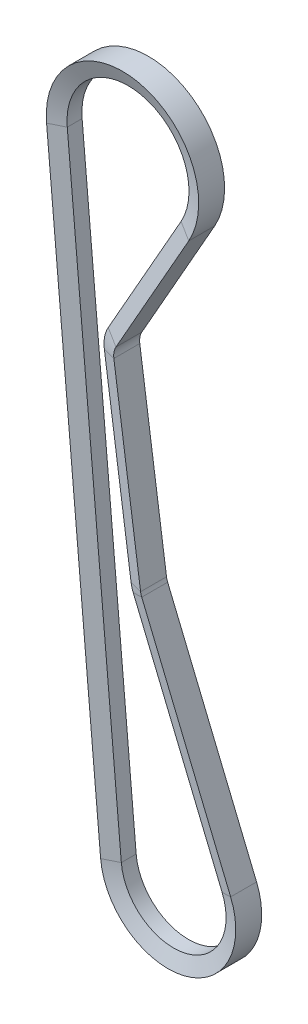
SolidWorks part; units mm, degrees
ref_plane "Front Plane" through (0, 0, 0) normal (0, 0, 1) x (1, 0, 0)
ref_plane "Top Plane" through (0, 0, 0) normal (0, 1, 0) x (1, 0, 0)
ref_plane "Right Plane" through (0, 0, 0) normal (1, 0, 0) x (0, 0, -1)
sketch "Sketch2" plane through (0, 0, 0) normal (0, 0, 1) x (1, 0, 0)
  line L0 (0, 0) -> (1, 0) construction
  line L1 (0, 0) -> (0, 1) construction
  line L12 (-24.7779, -2.1962) -> (-44.6411, 221.9035)
  line L14 (7.6011, 210.5552) -> (-19.1583, 163.4053)
  line L15 (-19.9228, 159.3796) -> (-10.0954, 90.0729)
  line L16 (-9.6768, 88.5389) -> (22.989, 9.5012)
  arc A4 (-44.6411, 221.9035) -> (7.6011, 210.5552) centre (-16.7504, 224.3756) cw
  arc A7 (22.989, 9.5012) -> (-24.7779, -2.1962) centre (0, 0) cw
  arc A8 (-19.1583, 163.4053) -> (-19.9228, 159.3796) centre (-13.6357, 160.2711) ccw
  arc A9 (-10.0954, 90.0729) -> (-9.6768, 88.5389) centre (-3.8083, 90.9643) ccw
ref_plane "Plane4" through (22.989, 9.5012, 0) normal (0.382, -0.9242, 0) x (-0.9242, -0.382, 0)
sketch "Sketch3" plane through (22.989, 9.5012, 0) normal (0.382, -0.9242, 0) x (-0.9242, -0.382, 0)
  line L0 (0, -4.7625) -> (0, 4.7625)
  line L1 (0, -4.7625) -> (5.588, -2.7286)
  line L2 (5.588, -2.7286) -> (5.588, 2.7286)
  line L3 (5.588, 2.7286) -> (0, 4.7625)
  line L4 (0, 0) -> (5.588, 0) construction
  dimension "D1" = 9.525
  dimension "D2" = 5.588
  dimension "D3" = 40
sweep "Sweep1" add profiles "Sketch3" path "Sketch2"
